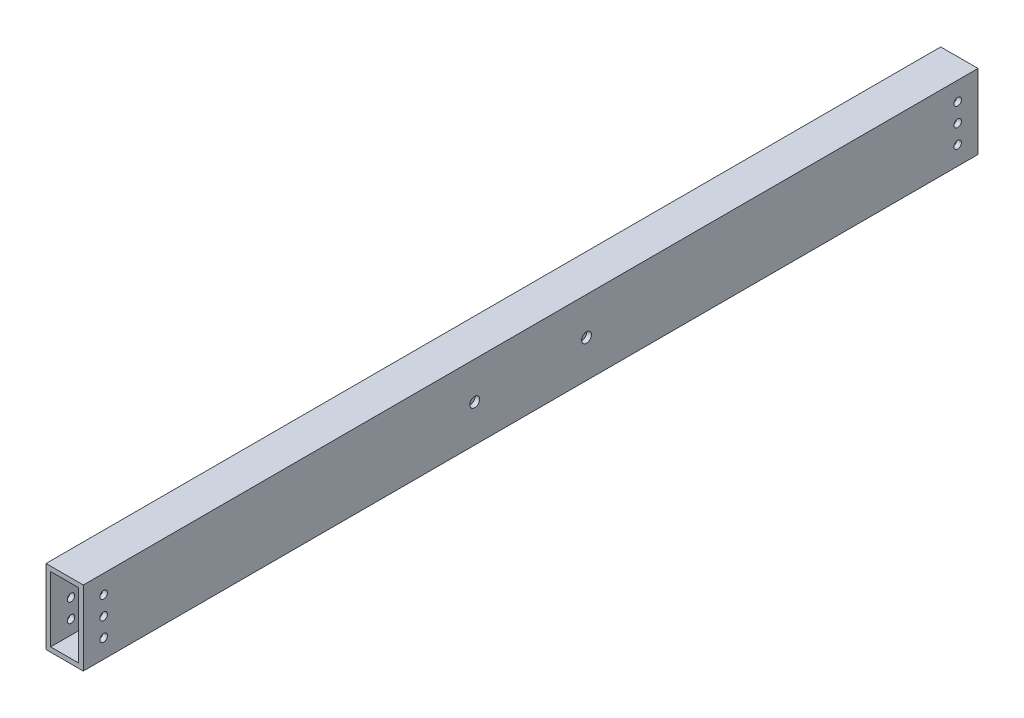
SolidWorks part; units mm, degrees
ref_plane "Front Plane" through (0, 0, 0) normal (0, 0, 1) x (1, 0, 0)
ref_plane "Top Plane" through (0, 0, 0) normal (0, 1, 0) x (1, 0, 0)
ref_plane "Right Plane" through (0, 0, 0) normal (1, 0, 0) x (0, 0, -1)
sketch "Sketch1" plane through (0, 0, 0) normal (0, 0, 1) x (1, 0, 0)
  line L0 (-9.525, 22.225) -> (9.525, 22.225)
  line L1 (-12.7, 25.4) -> (12.7, 25.4)
  line L2 (-12.7, 25.4) -> (-12.7, -25.4)
  line L3 (-12.7, -25.4) -> (12.7, -25.4)
  line L4 (12.7, 25.4) -> (12.7, -25.4)
  line L5 (-12.7, 25.4) -> (12.7, -25.4) construction
  line L6 (-12.7, -25.4) -> (12.7, 25.4) construction
  line L7 (9.525, 22.225) -> (9.525, -22.225)
  line L8 (-9.525, -22.225) -> (9.525, -22.225)
  line L9 (-9.525, 22.225) -> (-9.525, -22.225)
  point P0 (0, 0)
  dimension "D1" = 50.8
  dimension "D2" = 25.4
  dimension "D3" = 3.175
extrude "Boss-Extrude1" add sketch "Sketch1" along normal mid plane 609.6
hole_wizard "#10 Clearance Hole1" positions "Sketch4" profile "Sketch3" hole size "#10" standard "ANSI Inch" end condition through all
sketch "Sketch4" plane through (12.7, 0, 0) normal (1, 0, 0) x (0, 0, -1)
  line L0 (-304.8, 25.4) -> (304.8, 25.4) construction
  point P0 (-290.9409, 12.7)
  point P13 (-290.9409, 0)
  point P14 (-290.9409, -12.7)
  dimension "D2" = 12.7
  dimension "D1" = 3
sketch "Sketch3" plane through (12.7, 12.7, 290.9409) normal (0, 1, 0) x (0, 0, -1)
  line L0 (0, 0) -> (0, 25.4)
  line L1 (0, 25.4) -> (2.5527, 25.4)
  line L2 (2.5527, 25.4) -> (2.5527, 0)
  line L5 (2.5527, 0) -> (0, 0)
  line L11 (0, -6.35) -> (0, 107.95) construction
  dimension "Thru Hole Dia." = 5.1054
  dimension "Thru Hole Depth" = 25.4
mirror "Mirror1" about plane through (0, 0, 0) normal (0, 0, 1) of "#10 Clearance Hole1"
hole_wizard "1/4 Clearance Hole2" positions "Sketch6" profile "Sketch5" hole size "1/4" standard "ANSI Inch" end condition through all
sketch "Sketch6" plane through (12.7, 0, 0) normal (1, 0, 0) x (0, 0, -1)
  line L0 (-38.1, 0) -> (38.1, 0) construction
  point P0 (-38.1, 0)
  point P2 (38.1, 0)
  dimension "D1" = 76.2
sketch "Sketch5" plane through (12.7, 0, 38.1) normal (0, 1, 0) x (0, 0, -1)
  line L0 (0, 0) -> (0, 25.4)
  line L1 (0, 25.4) -> (3.3782, 25.4)
  line L2 (3.3782, 25.4) -> (3.3782, 0)
  line L5 (3.3782, 0) -> (0, 0)
  line L11 (0, -6.35) -> (0, 107.95) construction
  dimension "Thru Hole Dia." = 6.7564
  dimension "Thru Hole Depth" = 25.4
